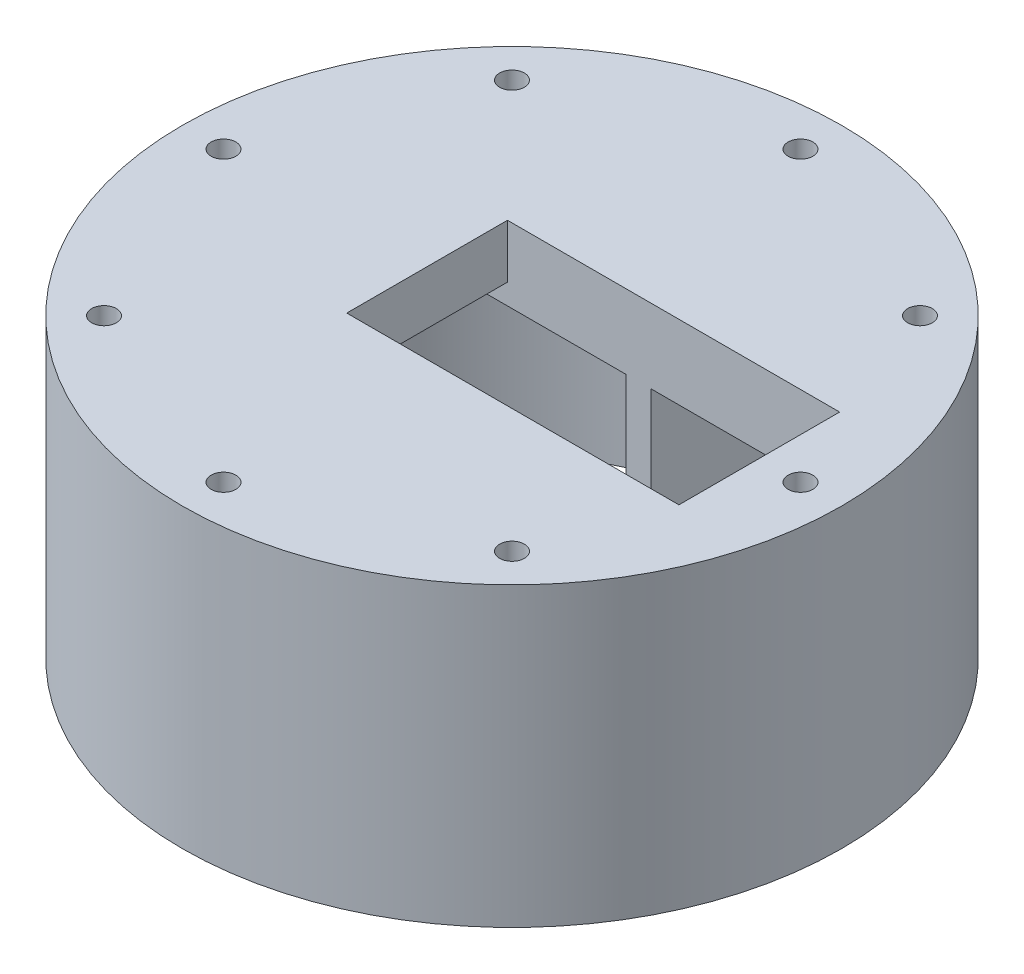
SolidWorks part; units mm, degrees
ref_plane "Front Plane" through (0, 0, 0) normal (0, 0, 1) x (1, 0, 0)
ref_plane "Top Plane" through (0, 0, 0) normal (0, 1, 0) x (1, 0, 0)
ref_plane "Right Plane" through (0, 0, 0) normal (1, 0, 0) x (0, 0, -1)
sketch "Sketch1" plane through (0, 0, 0) normal (0, 1, 0) x (1, 0, 0)
  line L0 (-43.0464, 0) -> (41.9462, 0) construction
  line L1 (0, 43.1152) -> (0, -41.8775) construction
  circle A0 centre (0, 0) radius 9.5
  circle A1 centre (0, 0) radius 40
  dimension "D1" = 19
  dimension "D2" = 80
extrude "Boss-Extrude1" add sketch "Sketch1" along normal blind 36
sketch "Sketch2" plane through (0, 0, 0) normal (0, -1, 0) x (1, 0, 0)
  circle A0 centre (0, 0) radius 30
  dimension "D1" = 60
extrude "Cut-Extrude1" cut sketch "Sketch2" against normal blind 27
sketch "Sketch3" plane through (0, 27, 0) normal (0, -1, 0) x (1, 0, 0)
  line L0 (30, 0) -> (-30, 0) construction
  line L1 (0, -30) -> (0, 30) construction
  line L3 (36.85, -9.75) -> (-17.15, -9.75)
  line L4 (36.85, -9.75) -> (36.85, 9.75)
  line L5 (36.85, 9.75) -> (-17.15, 9.75)
  line L6 (-17.15, -9.75) -> (-17.15, 9.75)
  circle A0 centre (0, 0) radius 30 construction
  circle A1 centre (0, 0) radius 30 construction
  dimension "D1" = 19.5
  dimension "D2" = 54
  dimension "D3" = 9.75
  dimension "D4" = 36.85
extrude "Cut-Extrude2" cut sketch "Sketch3" against normal blind 2.5 and the other way up to next
sketch "Sketch4" plane through (0, 29.5, 0) normal (0, -1, 0) x (1, 0, 0)
  line L0 (36.85, 0) -> (-17.15, 0) construction
  line L1 (36.85, 9.75) -> (36.85, -9.75) construction
  line L2 (-17.15, 9.75) -> (-17.15, -9.75) construction
  line L3 (0, -9.75) -> (0, 9.75) construction
  line L4 (-17.15, -9.75) -> (28.3714, -9.75) construction
  line L5 (28.3714, 9.75) -> (-17.15, 9.75) construction
  line L7 (30, -9.75) -> (-10.3, -9.75)
  line L8 (30, -9.75) -> (30, 9.75)
  line L9 (30, 9.75) -> (-10.3, 9.75)
  line L10 (-10.3, -9.75) -> (-10.3, 9.75)
  dimension "D1" = 19.5
  dimension "D2" = 40.3
  dimension "D3" = 30
  dimension "D4" = 9.75
extrude "Cut-Extrude3" cut sketch "Sketch4" against normal blind 6.5
sketch "Sketch8" plane through (0, 27, 0) normal (0, -1, 0) x (1, 0, 0)
  line L0 (-17.15, 0) -> (-30, 0) construction
  line L1 (-17.15, 9.75) -> (-17.15, -9.75) construction
  line L2 (5.6107, 9.75) -> (5.6107, 29.4707) construction
  line L3 (28.3714, 9.75) -> (-17.15, 9.75) construction
  line L4 (5.6107, -9.75) -> (5.6107, -29.3194) construction
  line L5 (-17.15, -9.75) -> (28.3714, -9.75) construction
  line L6 (4.1107, 9.75) -> (4.1107, 29.717)
  line L7 (7.1107, 9.75) -> (7.1107, 29.1451)
  line L8 (7.1107, 9.75) -> (4.1107, 9.75)
  line L9 (7.1107, -9.75) -> (4.1107, -9.75)
  line L10 (4.1107, -9.75) -> (4.1107, -29.717)
  line L11 (7.1107, -9.75) -> (7.1107, -29.1451)
  line L12 (-17.15, 1.5) -> (-29.9625, 1.5)
  line L13 (-17.15, -1.5) -> (-29.9625, -1.5)
  line L14 (-17.15, 1.5) -> (-17.15, -1.5)
  arc A0 (28.3714, 9.75) -> (28.3714, -9.75) centre (0, 0) ccw construction
  arc A1 (7.1107, 29.1451) -> (4.1107, 29.717) centre (5.5562, 29.1451) ccw
  arc A2 (7.1107, -29.1451) -> (4.1107, -29.717) centre (5.5562, -29.1451) cw
  arc A3 (-29.9625, 1.5) -> (-29.9625, -1.5) centre (-29.9625, 0) ccw
  dimension "D3" = 1.5
  dimension "D1" = 1.5
  dimension "D2" = 1.5
  dimension "D4" = 1.5
extrude "Boss-Extrude2" add sketch "Sketch8" along normal through all
sketch "Sketch9" plane through (0, 36, 0) normal (0, 1, 0) x (1, 0, 0)
  circle A0 centre (0, 0) radius 35 construction
  circle A1 centre (0, 35) radius 1.5
  circle A2 centre (24.7487, 24.7487) radius 1.5
  circle A3 centre (35, 0) radius 1.5
  circle A4 centre (24.7487, -24.7487) radius 1.5
  circle A5 centre (0, -35) radius 1.5
  circle A6 centre (-24.7487, -24.7487) radius 1.5
  circle A7 centre (-35, 0) radius 1.5
  circle A8 centre (-24.7487, 24.7487) radius 1.5
  point P5 (0, 0)
  point P22 (0, 0)
  dimension "D1" = 70
  dimension "D2" = 3
  dimension "D3" = 8
extrude "Cut-Extrude4" cut sketch "Sketch9" against normal through all
sketch "Sketch10" plane through (0, 0, 0) normal (0, -1, 0) x (1, 0, 0)
  line L0 (-24.0016, -21.9603) -> (-26.79, -22.7075)
  line L1 (2.8868, -35) -> (1.4434, -32.5)
  line L2 (1.4434, -32.5) -> (-1.4434, -32.5)
  line L3 (-1.4434, -32.5) -> (-2.8868, -35)
  line L4 (-2.8868, -35) -> (-1.4434, -37.5)
  line L5 (-1.4434, -37.5) -> (1.4434, -37.5)
  line L6 (1.4434, -37.5) -> (2.8868, -35)
  line L7 (-26.79, -22.7075) -> (-27.5371, -25.4959)
  line L8 (-27.5371, -25.4959) -> (-25.4959, -27.5371)
  line L9 (-25.4959, -27.5371) -> (-22.7075, -26.79)
  line L10 (-22.7075, -26.79) -> (-21.9603, -24.0016)
  line L11 (-21.9603, -24.0016) -> (-24.0016, -21.9603)
  line L12 (-32.5, 1.4434) -> (-35, 2.8868)
  line L13 (-35, 2.8868) -> (-37.5, 1.4434)
  line L14 (-37.5, 1.4434) -> (-37.5, -1.4434)
  line L15 (-37.5, -1.4434) -> (-35, -2.8868)
  line L16 (-35, -2.8868) -> (-32.5, -1.4434)
  line L17 (-32.5, -1.4434) -> (-32.5, 1.4434)
  line L18 (-21.9603, 24.0016) -> (-22.7075, 26.79)
  line L19 (-22.7075, 26.79) -> (-25.4959, 27.5371)
  line L20 (-25.4959, 27.5371) -> (-27.5371, 25.4959)
  line L21 (-27.5371, 25.4959) -> (-26.79, 22.7075)
  line L22 (-26.79, 22.7075) -> (-24.0016, 21.9603)
  line L23 (-24.0016, 21.9603) -> (-21.9603, 24.0016)
  line L24 (1.4434, 32.5) -> (2.8868, 35)
  line L25 (2.8868, 35) -> (1.4434, 37.5)
  line L26 (1.4434, 37.5) -> (-1.4434, 37.5)
  line L27 (-1.4434, 37.5) -> (-2.8868, 35)
  line L28 (-2.8868, 35) -> (-1.4434, 32.5)
  line L29 (-1.4434, 32.5) -> (1.4434, 32.5)
  line L30 (24.0016, 21.9603) -> (26.79, 22.7075)
  line L31 (26.79, 22.7075) -> (27.5371, 25.4959)
  line L32 (27.5371, 25.4959) -> (25.4959, 27.5371)
  line L33 (25.4959, 27.5371) -> (22.7075, 26.79)
  line L34 (22.7075, 26.79) -> (21.9603, 24.0016)
  line L35 (21.9603, 24.0016) -> (24.0016, 21.9603)
  line L36 (32.5, -1.4434) -> (35, -2.8868)
  line L37 (35, -2.8868) -> (37.5, -1.4434)
  line L38 (37.5, -1.4434) -> (37.5, 1.4434)
  line L39 (37.5, 1.4434) -> (35, 2.8868)
  line L40 (35, 2.8868) -> (32.5, 1.4434)
  line L41 (32.5, 1.4434) -> (32.5, -1.4434)
  line L42 (21.9603, -24.0016) -> (22.7075, -26.79)
  line L43 (22.7075, -26.79) -> (25.4959, -27.5371)
  line L44 (25.4959, -27.5371) -> (27.5371, -25.4959)
  line L45 (27.5371, -25.4959) -> (26.79, -22.7075)
  line L46 (26.79, -22.7075) -> (24.0016, -21.9603)
  line L47 (24.0016, -21.9603) -> (21.9603, -24.0016)
  circle A0 centre (0, -35) radius 2.5 construction
  point P54 (0, 0)
  dimension "D1" = 5
  dimension "D2" = 8
extrude "Cut-Extrude5" cut sketch "Sketch10" against normal blind 33
